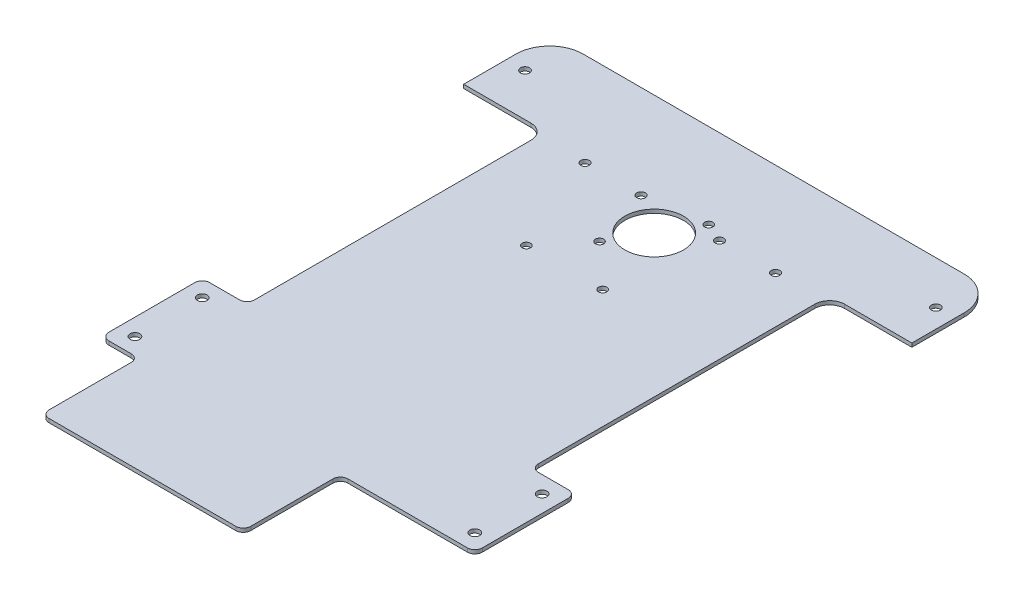
SolidWorks part; units mm, degrees
material "Thornel VCB-20 Carbon Cloth"
ref_plane "Front" through (0, 0, 0) normal (0, 0, 1) x (1, 0, 0)
ref_plane "Top" through (0, 0, 0) normal (0, 1, 0) x (1, 0, 0)
ref_plane "Right" through (0, 0, 0) normal (1, 0, 0) x (0, 0, -1)
ref_axis "X" through (-80.9, 0, 0) along (1, 0, 0)
ref_axis "Y" through (0, -50, 0) along (0, 1, 0)
ref_axis "Z" through (0, 0, -80.9) along (0, 0, 1)
sketch "Sketch1" plane through (0, 0, 0) normal (0, 1, 0) x (1, 0, 0)
  line L0 (-50, -130) -> (-40, -130)
  line L1 (-50, -130) -> (-50, -103)
  line L2 (-50, -103) -> (-38, -103)
  line L3 (-38, -103) -> (-38, -23)
  line L4 (-38, -23) -> (-60, -23)
  line L5 (-60, -23) -> (-60, 0)
  line L6 (-60, 0) -> (60, 0)
  line L7 (60, 0) -> (60, -23)
  line L8 (60, -23) -> (38, -23)
  line L9 (38, -23) -> (38, -103)
  line L10 (38, -103) -> (50, -103)
  line L11 (50, -103) -> (50, -130)
  line L12 (0, -162) -> (0, 0) construction
  line L13 (-40, -130) -> (-40, -156)
  line L14 (-40, -156) -> (14, -156)
  line L15 (14, -156) -> (14, -130)
  line L16 (14, -130) -> (50, -130)
  line L17 (-13, -156) -> (-13, -145.4675) construction
  dimension "D1" = 100
  dimension "D2" = 76
  dimension "D3" = 27
  dimension "D4" = 90
  dimension "D5" = 23
  dimension "D6" = 120
  dimension "D7" = 130
  dimension "D8" = 54
  dimension "D9" = 26
  dimension "D10" = 13
extrude "Boss-Extrude1" add sketch "Sketch1" along normal mid plane 1
hole_wizard "M2 Clearance Hole1" positions "Sketch2" profile "Sketch3" hole size "M2" standard "ANSI Metric" end condition up to next
sketch "Sketch2" plane through (0, 0.5, 0) normal (0, 1, 0) x (1, 0, 0)
  line L0 (-45.5, -125.5) -> (45.5, -125.5) construction
  line L2 (-50, -130) -> (-40, -130) construction
  line L3 (-50, -103) -> (-50, -130) construction
  line L4 (50, -130) -> (50, -103) construction
  line L5 (-45.5, -107.5) -> (-45.5, -125.5) construction
  line L8 (45.5, -107.5) -> (45.5, -125.5) construction
  point P0 (-45.5, -125.5)
  point P2 (45.5, -125.5)
  point P15 (-45.5, -107.5)
  point P17 (45.5, -107.5)
  dimension "D1" = 4.5
  dimension "D2" = 4.5
  dimension "D3" = 4.5
  dimension "D4" = 18
sketch "Sketch3" plane through (-45.5, 0.5, 125.5) normal (1, 0, 0) x (0, 0, 1)
  line L0 (0, 0) -> (0, 1)
  line L1 (0, 1) -> (1.3, 1)
  line L2 (1.3, 1) -> (1.3, 0)
  line L5 (1.3, 0) -> (0, 0)
  line L11 (0, -6.35) -> (0, 107.95) construction
  dimension "Thru Hole Dia." = 2.6
  dimension "Thru Hole Depth" = 1
fillet "Fillet1" radius 2 6 edges at (-50, 0, 130) (50, 0, 103) (-50, 0, 103) (-40, 0, 156) (14, 0, 156) (50, 0, 130)
fillet "Fillet2" radius 9 2 edges at (60, 0, 0) (-60, 0, 0)
hole_wizard "M2 Clearance Hole2" positions "Sketch7" profile "Sketch8" hole size "M2" standard "ANSI Metric" end condition up to next
sketch "Sketch7" plane through (0, 0.5, 0) normal (0, 1, 0) x (1, 0, 0)
  line L0 (-55, -11.57) -> (55, -11.57) construction
  line L2 (0, 0) -> (0, -11.57) construction
  line L3 (51, 0) -> (-51, 0) construction
  line L5 (-60, -23) -> (-38, -23) construction
  point P0 (-55, -11.57)
  point P2 (55, -11.57)
  dimension "D1" = 110
  dimension "D2" = 11.43
sketch "Sketch8" plane through (-55, 0.5, 11.57) normal (1, 0, 0) x (0, 0, 1)
  line L0 (0, 0) -> (0, 1)
  line L1 (0, 1) -> (1.2, 1)
  line L2 (1.2, 1) -> (1.2, 0)
  line L5 (1.2, 0) -> (0, 0)
  line L11 (0, -6.35) -> (0, 107.95) construction
  dimension "Thru Hole Dia." = 2.4
  dimension "Thru Hole Depth" = 1
fillet "Fillet4" radius 2 4 edges at (38, 0, 103) (-38, 0, 103) (14, 0, 130) (-40, 0, 130)
fillet "Fillet5" radius 4 2 edges at (38, 0, 23) (-38, 0, 23)
sketch "Sketch13" plane through (0, 0.5, 0) normal (0, 1, 0) x (1, 0, 0)
  line L0 (-38, -111) -> (-38, -122) construction
  line L1 (-35, -111) -> (-35, -122)
  line L3 (38, -111) -> (38, -122) construction
  line L5 (35, -111) -> (35, -122)
  line L6 (-38, -116.5) -> (38, -116.5) construction
  line L7 (0, -116.5) -> (0, 0) construction
  line L8 (51, 0) -> (-51, 0) construction
  line L11 (-45.5, -107.5) -> (-45.5, -125.5) construction
  line L12 (-45.5, -116.5) -> (-38, -116.5) construction
  line L13 (-38, -108) -> (-45.5, -108)
  line L14 (-38, -125) -> (-45.5, -125)
  line L15 (38, -108) -> (45.5, -108)
  line L16 (38, -125) -> (45.5, -125)
  line L17 (48.5, -111) -> (48.5, -122)
  line L18 (-48.5, -111) -> (-48.5, -122)
  line L19 (-35, -116.5) -> (-48.5, -116.5) construction
  line L20 (35, -116.5) -> (48.5, -116.5) construction
  arc A0 (-35, -111) -> (-38, -108) centre (-38, -111) ccw
  arc A1 (-38, -125) -> (-35, -122) centre (-38, -122) ccw
  arc A2 (38, -108) -> (35, -111) centre (38, -111) ccw
  arc A3 (35, -122) -> (38, -125) centre (38, -122) ccw
  circle A4 centre (-45.5, -107.5) radius 1.3 construction
  arc A5 (45.5, -108) -> (48.5, -111) centre (45.5, -111) cw
  arc A6 (48.5, -122) -> (45.5, -125) centre (45.5, -122) cw
  arc A7 (-45.5, -108) -> (-48.5, -111) centre (-45.5, -111) ccw
  arc A8 (-48.5, -122) -> (-45.5, -125) centre (-45.5, -122) ccw
  point P2 (-38, -116.5)
  point P8 (38, -116.5)
  dimension "D5" = 3.5
  dimension "D1" = 17
  dimension "D2" = 13.5
  dimension "D3" = 70
extrude "Cut-Extrude4" [suppressed] cut sketch "Sketch13" against normal through all
hole_wizard "M2 Clearance Hole3" positions "Sketch14" profile "Sketch15" hole size "M2" standard "ANSI Metric" end condition up to next
sketch "Sketch14" plane through (0, 0.5, 0) normal (0, 1, 0) x (1, 0, 0)
  line L2 (5.35, -22.7335) -> (-5.35, -41.2665) construction
  line L3 (0, 0) -> (0, -32) construction
  line L4 (51, 0) -> (-51, 0) construction
  point P0 (5.35, -22.7335)
  point P2 (-5.35, -41.2665)
  point P15 (0, -42.7)
  point P16 (1.105, -42.6428)
  point P17 (3.6869, -21.9553)
  dimension "D1" = 21.4
  dimension "D2" = 32
  dimension "D3" = 30
sketch "Sketch15" plane through (5.35, 0.5, 22.7335) normal (1, 0, 0) x (0, 0, 1)
  line L0 (0, 0) -> (0, 1)
  line L1 (0, 1) -> (1.1, 1)
  line L2 (1.1, 1) -> (1.1, 0)
  line L5 (1.1, 0) -> (0, 0)
  line L11 (0, -6.35) -> (0, 107.95) construction
  dimension "Thru Hole Dia." = 2.2
  dimension "Thru Hole Depth" = 1
sketch "Sketch17" plane through (0, 0.5, 0) normal (0, 1, 0) x (1, 0, 0)
  line L0 (-25.5, -25) -> (-10.5, -25) construction
  line L1 (-10.5, -25) -> (10.5, -25) construction
  line L2 (10.5, -25) -> (25.5, -25) construction
  line L4 (0, -25) -> (0, 0) construction
  line L5 (-18, -25) -> (-18, -29.652) construction
  line L7 (51, 0) -> (-51, 0) construction
  line L8 (18, -25) -> (18, -28.4507) construction
  circle A8 centre (25.5, -25) radius 1.15
  circle A9 centre (10.5, -25) radius 1.15
  circle A10 centre (-10.5, -25) radius 1.15
  circle A11 centre (-25.5, -25) radius 1.15
  dimension "D7" = 2.3
  dimension "D1" = 15
  dimension "D2" = 36
  dimension "D4" = 25
extrude "Cut-Extrude6" cut sketch "Sketch17" against normal through all
sketch "Sketch18" plane through (0, 0.5, 0) normal (0, 1, 0) x (1, 0, 0)
  line L0 (5.35, -22.7335) -> (-5.35, -41.2665) construction
  circle A0 centre (0, -32) radius 7.85
  circle A6 centre (5.35, -22.7335) radius 1.1 construction
  circle A8 centre (-5.35, -41.2665) radius 1.1 construction
  dimension "D3" = 15.7
extrude "Cut-Extrude7" cut sketch "Sketch18" against normal up to next
hole_wizard "M2 Clearance Hole4" positions "Sketch19" profile "Sketch20" hole size "M2" standard "ANSI Metric" end condition up to next
sketch "Sketch19" plane through (0, 0.5, 0) normal (0, 1, 0) x (1, 0, 0)
  line L0 (-14.21, -52) -> (6.21, -52) construction
  line L2 (0, 0) -> (0, -52) construction
  line L3 (51, 0) -> (-51, 0) construction
  point P0 (-14.21, -52)
  point P2 (6.21, -52)
  dimension "D1" = 20.42
  dimension "D2" = 6.21
  dimension "D3" = 52
sketch "Sketch20" plane through (-14.21, 0.5, 52) normal (1, 0, 0) x (0, 0, 1)
  line L0 (0, 0) -> (0, 1)
  line L1 (0, 1) -> (1.1, 1)
  line L2 (1.1, 1) -> (1.1, 0)
  line L5 (1.1, 0) -> (0, 0)
  line L11 (0, -6.35) -> (0, 107.95) construction
  dimension "Thru Hole Dia." = 2.2
  dimension "Thru Hole Depth" = 1
equation "\"dd\"=4"
